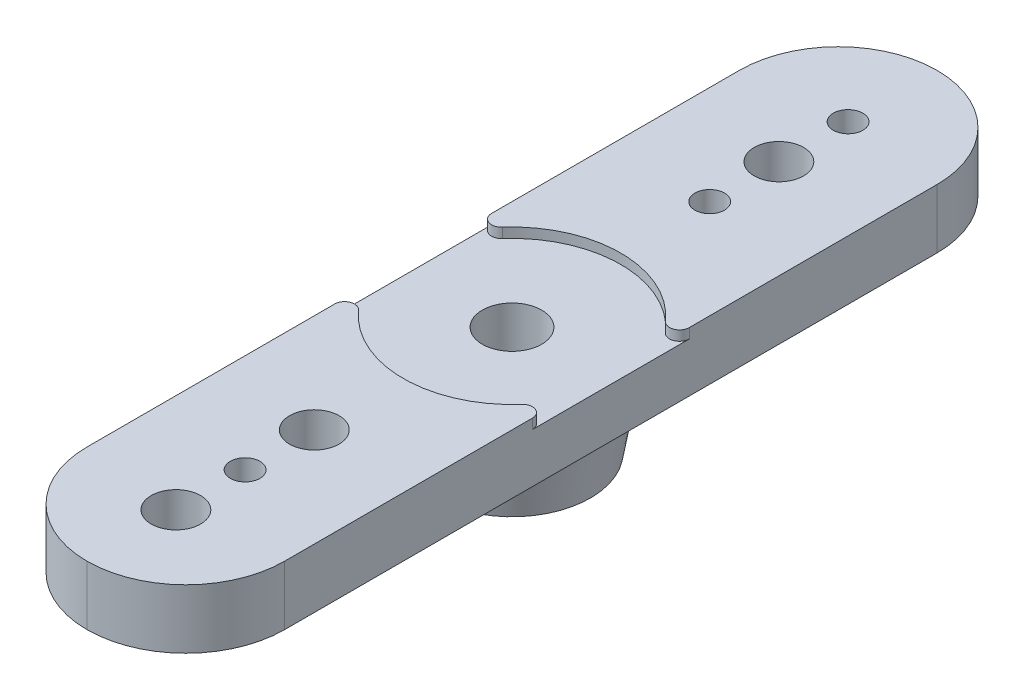
SolidWorks part; units mm, degrees
ref_plane "Front Plane" through (0, 0, 0) normal (0, 0, 1) x (1, 0, 0)
ref_plane "Top Plane" through (0, 0, 0) normal (0, 1, 0) x (1, 0, 0)
ref_plane "Right Plane" through (0, 0, 0) normal (1, 0, 0) x (0, 0, -1)
sketch "Sketch1" plane through (0, 0, 0) normal (0, 1, 0) x (1, 0, 0)
  line L1 (-5, 21.5) -> (5, 21.5)
  line L2 (-5, 21.5) -> (-5, -21.5)
  line L3 (-5, -21.5) -> (5, -21.5)
  line L4 (5, 21.5) -> (5, -21.5)
  point P4 (0, 21.5)
  point P6 (5, 0)
  dimension "D1" = 10
  dimension "D2" = 43
extrude "Boss-Extrude1" add sketch "Sketch1" along normal blind 3
fillet "Fillet1" radius 5 4 edges at (-5, 1.5, -21.5) (5, 1.5, -21.5) (5, 1.5, 21.5) (-5, 1.5, 21.5)
sketch "Sketch2" plane through (0, 0, 0) normal (0, 1, 0) x (1, 0, 0)
  circle A0 centre (0, 0) radius 4.5
  dimension "D1" = 9
extrude "Boss-Extrude2" add sketch "Sketch2" against normal blind 3
draft "Draft1" type of draft neutral plane draft angle 10 faces to draft 1 face at (0, -3, 4.5) neutral plane through (0, 0, 0) neutral plane normal (0, -1, 0) parameters "D1"=10
sketch "Sketch3" plane through (0, -3, 0) normal (0, -1, 0) x (1, 0, 0)
  circle A0 centre (0, 0) radius 3
  dimension "D1" = 6
extrude "Cut-Extrude1" cut sketch "Sketch3" against normal blind 3
sketch "Sketch4" plane through (0, 0, 0) normal (0, -1, 0) x (1, 0, 0)
  circle A0 centre (0, 0) radius 1.5
  dimension "D1" = 3
extrude "Cut-Extrude2" cut sketch "Sketch4" against normal through all
sketch "Sketch5" plane through (0, 3, 0) normal (0, 1, 0) x (1, 0, 0)
  circle A0 centre (0, 0) radius 5.5
  dimension "D1" = 11
extrude "Cut-Extrude3" cut sketch "Sketch5" against normal blind 0.5
fillet "Fillet2" radius 0.5 4 edges at (5, 2.75, 2.2913) (-5, 2.75, 2.2913) (5, 2.75, -2.2913) (-5, 2.75, -2.2913)
sketch "Sketch6" plane through (0, 3, 0) normal (0, 1, 0) x (1, 0, 0)
  line L0 (0, 10) -> (0, 17) construction
  line L1 (0, -17) -> (0, -10) construction
  circle A0 centre (0, 13.5) radius 1.25
  circle A1 centre (0, 17) radius 0.75
  circle A2 centre (0, 10) radius 0.75
  circle A3 centre (0, -17) radius 1.25
  circle A4 centre (0, -10) radius 1.25
  circle A5 centre (0, -13.5) radius 0.75
  point P7 (0, 0)
  dimension "D1" = 2.5
  dimension "D2" = 1.5
  dimension "D3" = 7
  dimension "D4" = 13.5
  dimension "D5" = 13.5
extrude "Cut-Extrude4" cut sketch "Sketch6" against normal through all
